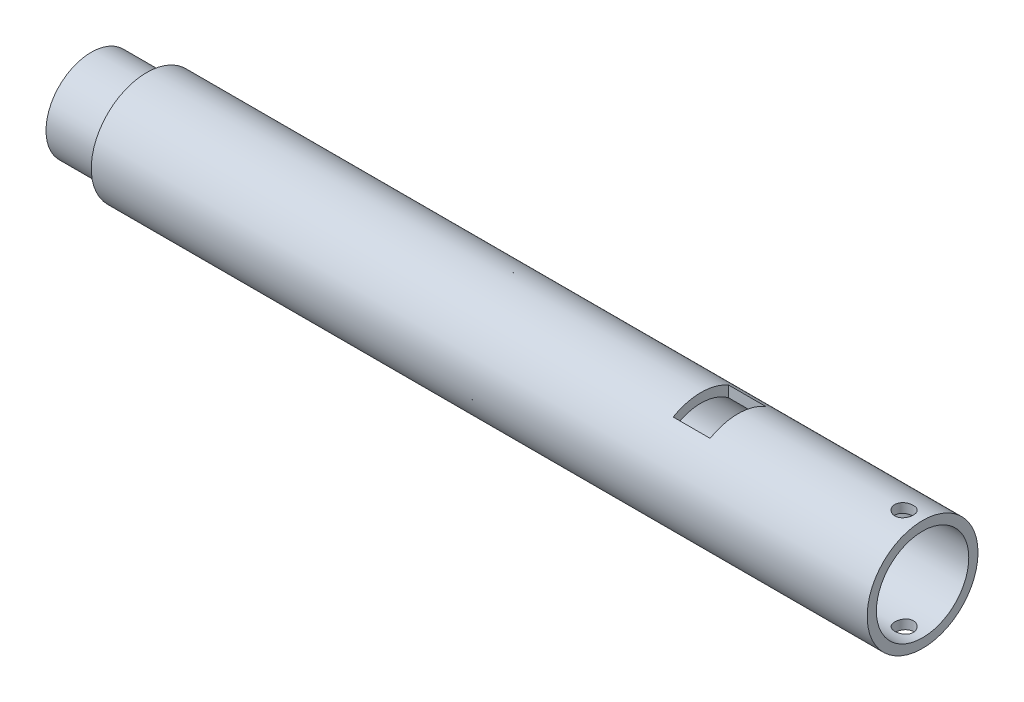
SolidWorks part; units mm, degrees
ref_plane "Plano frontal" through (0, 0, 0) normal (0, 0, 1) x (1, 0, 0)
ref_plane "Plano superior" through (0, 0, 0) normal (0, 1, 0) x (1, 0, 0)
ref_plane "Plano direito" through (0, 0, 0) normal (1, 0, 0) x (0, 0, -1)
sketch "Esboço1" plane through (0, 0, 0) normal (1, 0, 0) x (0, 0, -1)
  circle A0 centre (0, 0) radius 15
  circle A1 centre (0, 0) radius 12.5
  dimension "D1" = 30
  dimension "D2" = 25
extrude "Ressalto-extrusão1" add sketch "Esboço1" along normal blind 210 contours A1 | A0
sketch "Esboço2" plane through (0, 0, 0) normal (-1, 0, 0) x (0, 0, 1)
  line L0 (0, 15) -> (0, 0) construction
  circle A0 centre (0, 0) radius 15 construction
  circle A1 centre (0, 0) radius 10
  circle A3 centre (0, 0) radius 12.25
  dimension "D1" = 20
  dimension "D2" = 24.5
extrude "Ressalto-extrusão3" add sketch "Esboço2" against normal blind 15 from offset 15
sketch "Esboço4" plane through (0, 0, 0) normal (0, 1, 0) x (1, 0, 0)
  line L0 (-15, 12.25) -> (-15, -12.25) construction
  line L1 (210, -15) -> (210, 15) construction
  circle A0 centre (-10, 0.5) radius 2.5
  circle A1 centre (205, 0) radius 2.5
  dimension "D1" = 5
  dimension "D3" = 5
  dimension "D2" = 5
  dimension "D4" = 5
sketch "Esboço5" plane through (0, 0, 0) normal (0, 1, 0) x (1, 0, 0)
  line L0 (210, -15) -> (210, 15) construction
  circle A0 centre (205, 0) radius 2.5
  dimension "D1" = 5
  dimension "D2" = 5
sketch3d "3DSketch1"
  point P0 (150.2064, 4.5345, 11.6485)
extrude "Corte-extrusão2" cut sketch "Esboço4" against normal blind 300 and the other way blind 300 contours A1
sketch "Esboço6" plane through (0, 0, 0) normal (0, 1, 0) x (1, 0, 0)
  line L1 (150, 7.5) -> (160, 7.5)
  line L2 (150, 7.5) -> (150, -7.5)
  line L3 (150, -7.5) -> (160, -7.5)
  line L4 (160, 7.5) -> (160, -7.5)
  line L5 (150, 7.5) -> (160, -7.5) construction
  line L6 (150, -7.5) -> (160, 7.5) construction
  point P0 (155, 0)
extrude "Corte-extrusão4" cut sketch "Esboço6" along normal blind 20
sketch "Esboço7" plane through (0, 0, 0) normal (-1, 0, 0) x (0, 0, 1)
  line L0 (2.5, 0) -> (-2.5, 0) construction
  circle A0 centre (0, 0) radius 12.5
extrude "Ressalto-extrusão4" add sketch "Esboço7" against normal blind 10
sketch "Esboço11" plane through (0, 0, 0) normal (-1, 0, 0) x (0, 0, 1)
  circle A0 centre (0, 0) radius 10
extrude "Corte-extrusão8" cut sketch "Esboço11" against normal blind 20
